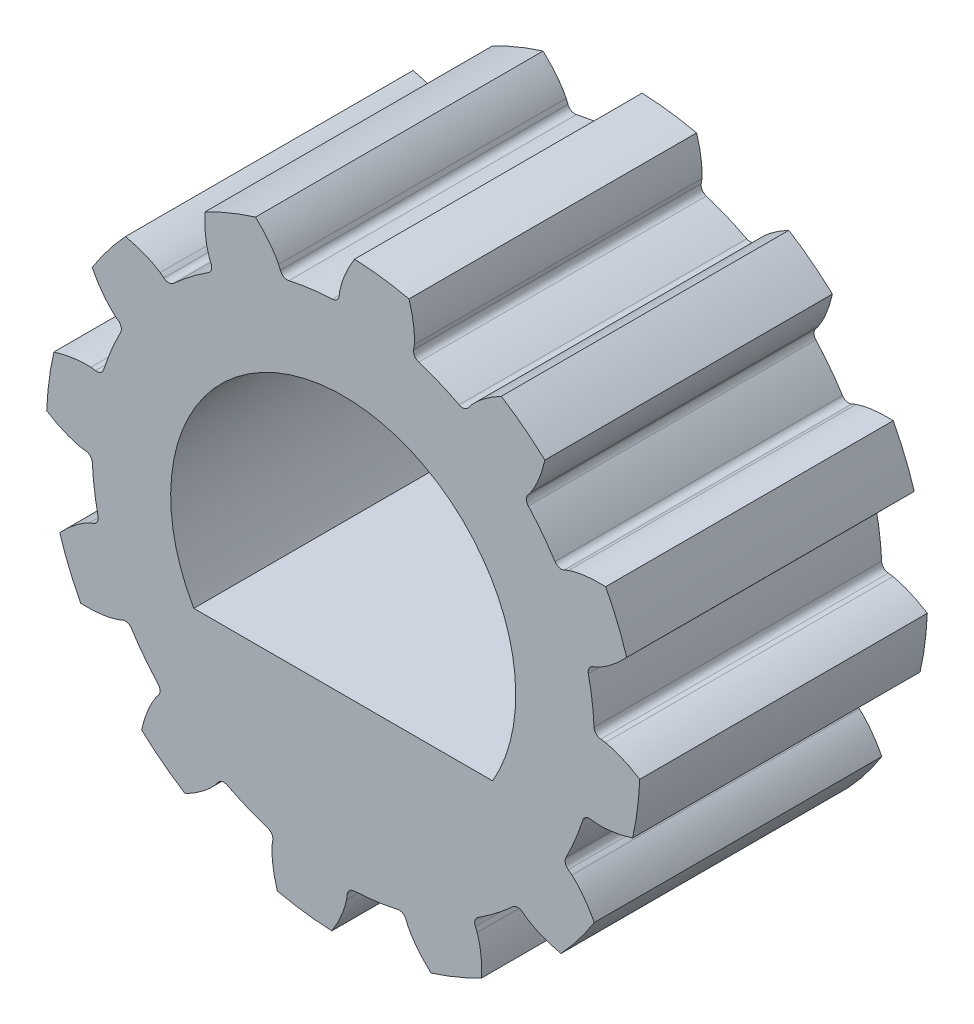
SolidWorks part; units mm, degrees
ref_plane "Front Plane" through (0, 0, 0) normal (0, 0, 1) x (1, 0, 0)
ref_plane "Top Plane" through (0, 0, 0) normal (0, 1, 0) x (1, 0, 0)
ref_plane "Right Plane" through (0, 0, 0) normal (1, 0, 0) x (0, 0, -1)
ref_axis "Axis1" through (0, 0, -2.75) along (0, 0, 1)
sketch "Sketch1" plane through (0, 0, 0) normal (0, 0, 1) x (1, 0, 0)
  circle A0 centre (0, 0) radius 4.3656 construction
  circle A1 centre (0, 0) radius 5.1594 construction
  circle A2 centre (0, 0) radius 4.7625 construction
  circle A3 centre (0, 0) radius 3.5719 construction
  dimension "D1" = 8.7312
  dimension "D2" = 9.525
  dimension "D3" = 10.3187
  dimension "D4" = 0.7937
sketch "Sketch2" plane through (0, 0, 0) normal (0, 1, 0) x (1, 0, 0)
  line L0 (0, 2.5) -> (0, -2.5) construction
  point P3 (0, 0)
  dimension "D1" = 5
sketch "Sketch3" plane through (0, 0, 0) normal (0, 0, 1) x (1, 0, 0)
  circle A0 centre (0, 0) radius 3.5719 construction
  circle A1 centre (0, 0) radius 4.3656 construction
  circle A2 centre (0, 0) radius 3.5719
  circle A3 centre (0, 0) radius 4.3656
extrude "Boss-Extrude1" add sketch "Sketch3" along normal up to vertex (2.5 mm away) and the other way up to vertex (2.5 mm away) up to point (0, 0, 2.5) other way up to point (0, 0, -2.5)
sketch "Sketch4" plane through (0, 0, 0) normal (0, 0, 1) x (1, 0, 0)
  line L0 (-1.6289, -4.7625) -> (0, -4.7625) construction
  line L1 (0, -4.7625) -> (1.6289, -4.7625) construction
  line L2 (-1.5306, -4.2054) -> (0, -4.7625) construction
  line L3 (0, -4.7625) -> (1.5306, -5.3196) construction
  line L4 (-1.5306, -4.2054) -> (0, 0) construction
  line L5 (0, 0) -> (-2.2219, -3.8848) construction
  line L6 (-2.2219, -3.8848) -> (-0.1465, -5.0718) construction
  line L7 (-4.1735, -1.6156) -> (-3.8389, -2.3003) construction
  line L8 (-3.393, -2.9182) -> (-3.8389, -2.3003) construction
  line L9 (-3.393, -2.9182) -> (-2.8487, -3.4515) construction
  line L10 (-2.8487, -3.4515) -> (-2.2219, -3.8848) construction
  line L11 (-2.2219, -3.8848) -> (-1.5306, -4.2054) construction
  line L12 (-2.8487, -3.4515) -> (-0.4171, -5.4585) construction
  line L13 (-3.393, -2.9182) -> (-0.8402, -5.8863) construction
  line L14 (-3.8389, -2.3003) -> (-1.435, -6.3121) construction
  line L15 (-4.1735, -1.6156) -> (-2.21, -6.6877) construction
  line L16 (-4.3871, -0.8842) -> (-3.1619, -6.9628) construction
  line L17 (-4.3871, -0.8842) -> (-4.1735, -1.6156) construction
  line L18 (-1.5306, -4.2054) -> (-0.795, -4.4041) construction
  line L19 (-0.795, -4.4041) -> (0.0581, -4.5581) construction
  line L20 (0, 0) -> (0, -3.5719) construction
  line L21 (0, 0) -> (-1.2433, -9.4435) construction
  line L22 (0.071, -4.365) -> (-1.1983, -4.1979)
  arc A0 (-1.5306, -4.2054) -> (-2.2219, -3.8848) centre (0, 0) cw construction
  arc A1 (-2.2219, -3.8848) -> (-2.8487, -3.4515) centre (0, 0) cw construction
  circle A2 centre (0, 0) radius 4.4753 construction
  circle A3 centre (0, 0) radius 4.7625 construction
  arc A4 (-2.8487, -3.4515) -> (-3.393, -2.9182) centre (0, 0) cw construction
  arc A5 (-3.393, -2.9182) -> (-3.8389, -2.3003) centre (0, 0) cw construction
  arc A6 (-3.8389, -2.3003) -> (-4.1735, -1.6156) centre (0, 0) cw construction
  arc A7 (-4.1735, -1.6156) -> (-4.3871, -0.8842) centre (0, 0) cw construction
  arc A8 (-1.5306, -4.2054) -> (-0.795, -4.4041) centre (0, 0) ccw construction
  arc A9 (0.0581, -4.5581) -> (0.071, -4.365) centre (-0.795, -4.4041) ccw
  circle A10 centre (0, 0) radius 3.5719 construction
  arc A11 (-1.2358, -4.3878) -> (-1.1983, -4.1979) centre (-0.372, -4.4598) cw
  arc A12 (-1.1441, -5.0309) -> (-0.197, -5.1556) centre (0, 0) ccw
  circle A13 centre (0, 0) radius 4.3656 construction
  circle A14 centre (0, 0) radius 5.1594 construction
  spline S0 degree 3 poles (-3.1619, -6.9628) (-2.5575, -6.8412) (-1.7317, -6.5454) (-0.8611, -5.9287) (-0.4333, -5.5014) (-0.1178, -5.0569) (0.0211, -4.7401) (0.0581, -4.5581) knots 0 0 0 0 0.43973 0.61339 0.756247 0.8683 1 1 1 1
  spline S1 degree 3 poles (1.2521, -7.544) (0.6997, -7.27) (-0.0214, -6.7706) (-0.7027, -5.9496) (-1.0053, -5.4261) (-1.195, -4.9151) (-1.2472, -4.5731) (-1.2358, -4.3878) knots 0 0 0 0 0.43973 0.61339 0.756247 0.8683 1 1 1 1
  point P23 (0, -4.4753)
  point P41 (-0.5637, -4.2815)
  point P50 (0.0941, -5.9524)
  dimension "D1" = 1.6289
  dimension "D2" = 20
  dimension "D3" = 0.762
  dimension "D4" = 2.3909
  dimension "D5" = 3.1529
  dimension "D6" = 3.9149
  dimension "D7" = 4.6769
  dimension "D8" = 5.4389
  dimension "D9" = 6.2009
  dimension "D10" = 0.762
  dimension "D11" = 0.8669
  dimension "D12" = 7.5
  dimension "D13" = 9.525
extrude "Boss-Extrude2" add sketch "Sketch4" along normal mid plane 5 contours S1 S0 A9 L22 A11 region at (-0.6154, -4.6741, 0)
fillet "Fillet1" radius 0.127 2 edges at (0.071, -4.365, 0) (-1.1983, -4.1979, 0)
pattern_circular "CirPattern1" count 12 over 360 about axis through (0, 0, -2.5) along (0, 0, 1) of "Boss-Extrude2", "Fillet1"
sketch "Sketch5" plane through (0, 0, 0) normal (0, 0, 1) x (1, 0, 0)
  line L0 (-2.5981, -1.5) -> (2.5981, -1.5)
  line L1 (0, -1.5) -> (0, 3) construction
  line L2 (3.5719, 0) -> (4.3656, 0) construction
  circle A2 centre (0, 0) radius 3
  circle A3 centre (0, 0) radius 3.9688
  circle A4 centre (0, 0) radius 3.5719 construction
  circle A5 centre (0, 0) radius 4.3656 construction
  point P14 (3.9688, 0)
  dimension "D1" = 6
  dimension "D2" = 4.5
extrude "Boss-Extrude3" add sketch "Sketch5" along normal mid plane 5 contours A2 | L0 A2 region at (0, -2.1151, 0) region at (-3.8565, 0, 0)
equation "\"Pitch_Diameter\"= \"Tooth Number\" * \"Tooth Pitch\""
equation "\"OD\"= \"Pitch_Diameter\" + \"Tooth Pitch\""
equation "\"Tooth Number\" = 12"
equation "\"Tooth Pitch\"= 1 / 32"
equation "\"ID\"= \"Pitch_Diameter\" - \"Tooth Pitch\""
equation "\"D2@Sketch1\"=\"Pitch_Diameter\""
equation "\"D3@Sketch1\"=\"OD\""
equation "\"D1@Sketch1\"=\"ID\""
equation "\"D4@Sketch1\"=\"Tooth Pitch\""
equation "\"Thicknes\"= 5mm"
equation "\"D1@Sketch2\"=\"Thicknes\""
equation "\"Contact_angle\" = 20"
equation "\"length\"= sin ( 20 ) * \"Pitch_Diameter\" / 2"
equation "\"D1@Sketch4\"= \"length\""
equation "\"D2@Sketch4\"=\"Contact_angle\""
equation "\"arbitrary\"=0.03"
equation "\"D3@Sketch4\"=\"arbitrary\""
equation "\"D4@Sketch4\"=\"arbitrary\"+\"length\""
equation "\"D5@Sketch4\"=\"arbitrary\"*2+\"length\""
equation "\"D6@Sketch4\"=\"arbitrary\"*3+\"length\""
equation "\"D7@Sketch4\"=\"arbitrary\"*4+\"length\""
equation "\"D8@Sketch4\"=\"length\"+\"arbitrary\"*5"
equation "\"D9@Sketch4\"=\"length\"+\"arbitrary\"*6"
equation "\"D10@Sketch4\"=\"arbitrary\""
equation "\"D11@Sketch4\"=\"length\"-\"arbitrary\""
equation "\"D12@Sketch4\"=360/\"Tooth Number\"/4"
equation "\"D13@Sketch4\"=\"Pitch_Diameter\""
equation "\"D1@Boss-Extrude2\"=\"Thicknes\""
equation "\"D1@CirPattern1\"=\"Tooth Number\""
equation "\"D1@Boss-Extrude3\"=\"Thicknes\""
equation "\"ID\" = \"Pitch_Diameter\""
equation "\"Thickness\"= 5mm"
